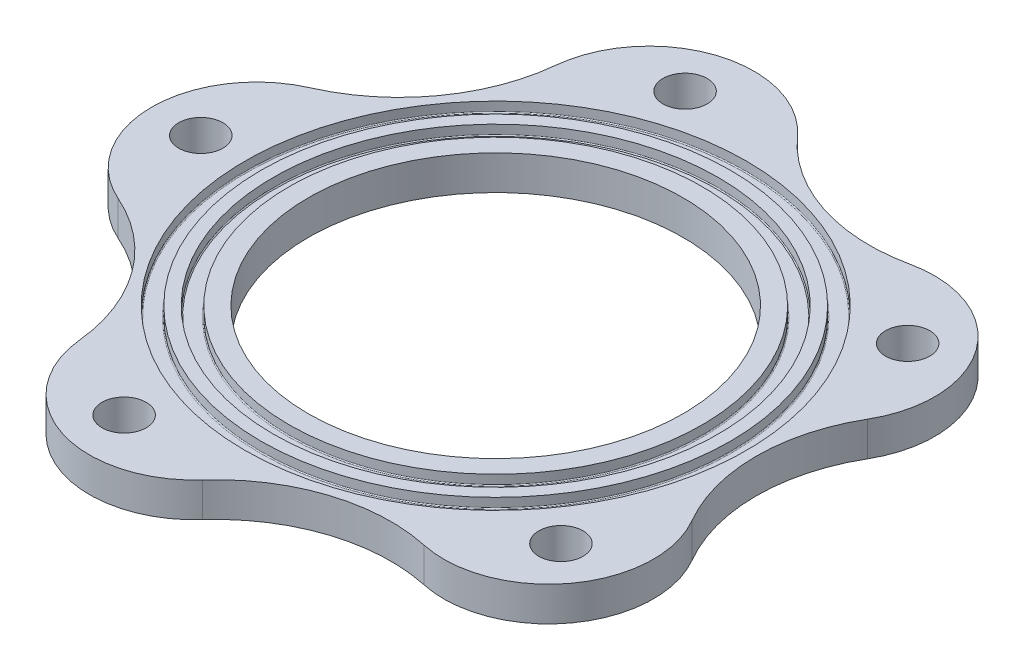
SolidWorks part; units mm, degrees
ref_plane "Front Plane" through (0, 0, 0) normal (0, 0, 1) x (1, 0, 0)
ref_plane "Top Plane" through (0, 0, 0) normal (0, 1, 0) x (1, 0, 0)
ref_plane "Right Plane" through (0, 0, 0) normal (1, 0, 0) x (0, 0, -1)
sketch "Sketch1" plane through (0, 0, 0) normal (0, 1, 0) x (1, 0, 0)
  circle A0 centre (0, 0) radius 38.1
  circle A9 centre (0, 0) radius 70
  circle A10 centre (0, 0) radius 47.4 construction
  dimension "D1" = 76.2
  dimension "D7" = 94.8
  dimension "D6" = 140
extrude "Boss-Extrude3" add sketch "Sketch1" along normal blind 7 contours A0 | A9 | A0 region at (-68.0201, 0, 0)
sketch "Sketch6" plane through (0, 0, 0) normal (1, 0, 0) x (0, 0, -1)
  line L0 (0, -6.7559) -> (0, 9.1132) construction
sketch "Sketch7" plane through (0, 0, 0) normal (0, 1, 0) x (1, 0, 0)
  line L0 (0, 0) -> (-70, 0) construction
  line L1 (-56.6312, -41.145) -> (0, 0) construction
  circle A0 centre (-48.541, -35.2671) radius 7 construction
  circle A1 centre (0, 0) radius 70 construction
  arc A2 (-42.8779, -31.1526) -> (-57.2762, -19.5288) centre (-71.6382, -52.0482) ccw
  circle A3 centre (-60, 0) radius 4.5 construction
  arc A4 (-42.8779, 31.1526) -> (-57.2762, 19.5288) centre (-71.6382, 52.0482) cw
  arc A6 (-57.2762, -19.5288) -> (-57.2762, 19.5288) centre (-48.6515, 0) cw
  circle A7 centre (0, 0) radius 70 construction
  circle A8 centre (0, 0) radius 70
  arc A9 (16.3779, 50.406) -> (0.8736, 60.5077) centre (27.3634, 84.2158) cw
  circle A10 centre (-18.541, 57.0634) radius 4.5 construction
  arc A11 (-36.2723, 48.4382) -> (0.8736, 60.5077) centre (-15.0341, 46.2703) cw
  arc A12 (-42.8779, 31.1526) -> (-36.2723, 48.4382) centre (-71.6382, 52.0482) ccw
  arc A13 (53, 0) -> (57.8162, 17.867) centre (88.5497, 0) cw
  circle A14 centre (48.541, 35.2671) radius 4.5 construction
  arc A15 (34.8587, 49.4652) -> (57.8162, 17.867) centre (39.3599, 28.5966) cw
  arc A16 (16.3779, 50.406) -> (34.8587, 49.4652) centre (27.3634, 84.2158) ccw
  arc A17 (16.3779, -50.406) -> (34.8587, -49.4652) centre (27.3634, -84.2158) cw
  circle A18 centre (48.541, -35.2671) radius 4.5 construction
  arc A19 (57.8162, -17.867) -> (34.8587, -49.4652) centre (39.3599, -28.5966) cw
  arc A20 (53, 0) -> (57.8162, -17.867) centre (88.5497, 0) ccw
  arc A21 (-42.8779, -31.1526) -> (-36.2723, -48.4382) centre (-71.6382, -52.0482) cw
  circle A22 centre (-18.541, -57.0634) radius 4.5 construction
  arc A23 (0.8736, -60.5077) -> (-36.2723, -48.4382) centre (-15.0341, -46.2703) cw
  arc A24 (16.3779, -50.406) -> (0.8736, -60.5077) centre (27.3634, -84.2158) ccw
  point P60 (0, 0)
  dimension "D1" = 9
  dimension "D3" = 14
  dimension "D2" = 60
  dimension "D4" = 36
  dimension "D5" = 60
  dimension "D6" = 18
  dimension "D7" = 5
extrude "Cut-Extrude8" cut sketch "Sketch7" along normal through all contours A4 A12 A11 A8 A6 | A8 A23 A21 A2 A6 | A17 A24 A23 A8 A19 | A13 A20 A19 A8 A15 | A10 | A9 A16 A15 A8 A11 region at (-50.178, 0, 36.4564) region at (-50.178, 0, -36.4564) region at (19.1663, 0, 58.9877) region at (19.1663, 0, -58.9877) region at (62.0234, 0, 0)
sketch "Sketch10" plane through (0, 0, 0) normal (0, -1, 0) x (1, 0, 0)
  circle A0 centre (-60, 0) radius 4.5 construction
  circle A1 centre (-60, 0) radius 4.5
extrude "Cut-Extrude10" cut sketch "Sketch10" against normal through all
pattern_circular "CirPattern1" count 5 over 360 about axis through (0, -6.7559, 0) along (0, 1, 0) of "Cut-Extrude10"
sketch "Sketch9" plane through (0, 7, 0) normal (0, 1, 0) x (1, 0, 0)
  circle A0 centre (0, 0) radius 42
  circle A1 centre (0, 0) radius 45.25
  circle A2 centre (0, 0) radius 47.75
  circle A3 centre (0, 0) radius 51
  dimension "D1" = 84
  dimension "D2" = 3.25
  dimension "D3" = 95.5
  dimension "D4" = 3.25
extrude "Cut-Extrude9" cut sketch "Sketch9" against normal blind 2 contours A3 A2 | A1 A0 region at (-43.9701, 7, 0) region at (-49.5575, 7, 0)
fillet "Fillet1" radius 0.2 4 edges at (0, 5, 45.25) (0, 5, 42) (0, 5, 51) (0, 5, 47.75)
equation "\"Bolt\"= 10'number of bolts"
equation "\"D4@Sketch7\"=360/\"Bolt\""
